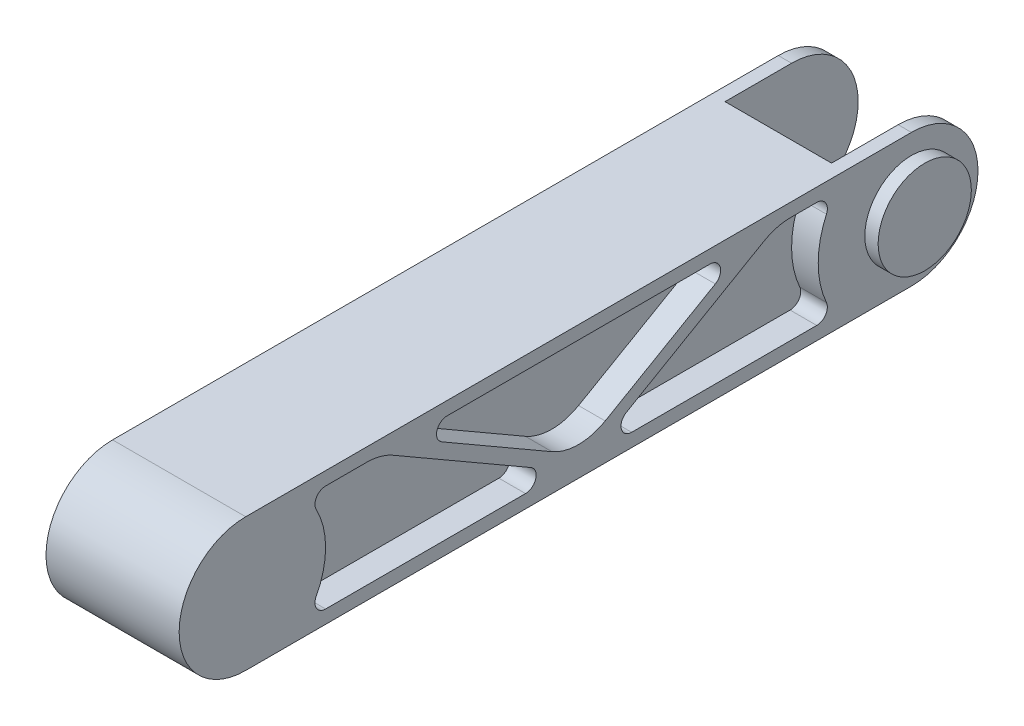
SolidWorks part; units mm, degrees
ref_plane "Front Plane" through (0, 0, 0) normal (0, 0, 1) x (1, 0, 0)
ref_plane "Top Plane" through (0, 0, 0) normal (0, 1, 0) x (1, 0, 0)
ref_plane "Right Plane" through (0, 0, 0) normal (1, 0, 0) x (0, 0, -1)
sketch "Sketch1" plane through (0, 0, 0) normal (1, 0, 0) x (0, 0, -1)
  line L1 (-125, -25) -> (125, -25)
  line L2 (-125, -25) -> (-125, 25) construction
  line L3 (-125, 25) -> (125, 25)
  line L4 (125, -25) -> (125, 25) construction
  line L5 (-125, -25) -> (125, 25) construction
  line L6 (-125, 25) -> (125, -25) construction
  arc A0 (125, 25) -> (125, -25) centre (125, 0) cw
  arc A1 (-125, 25) -> (-125, -25) centre (-125, 0) ccw
  point P0 (0, 0)
  point P8 (0, 0)
  point P9 (0, 0)
  dimension "D1" = 250
  dimension "D2" = 50
extrude "Boss-Extrude1" add sketch "Sketch1" along normal blind 25 and the other way blind 25
sketch "Sketch2" plane through (0, 25, 0) normal (0, 1, 0) x (1, 0, 0)
  line L0 (25, 150) -> (-25, 150) construction
  line L1 (-20, 200) -> (20, 200)
  line L2 (-20, 200) -> (-20, 100)
  line L3 (-20, 100) -> (20, 100)
  line L4 (20, 200) -> (20, 100)
  line L5 (-20, 200) -> (20, 100) construction
  line L6 (-20, 100) -> (20, 200) construction
  point P0 (0, 150)
  dimension "D1" = 40
  dimension "D2" = 50
extrude "Cut-Extrude1" cut sketch "Sketch2" against normal through all both and the other way through all
sketch "Sketch3" plane through (25, 0, 0) normal (1, 0, 0) x (0, 0, -1)
  line L0 (125, 25) -> (125, -25) construction
  circle A0 centre (125, 0) radius 17.5
  dimension "D1" = 35
extrude "Boss-Extrude2" add sketch "Sketch3" along normal blind 5
mirror "Mirror1" about plane through (0, 0, 0) normal (1, 0, 0) of "Boss-Extrude2"
sketch "Sketch4" plane through (25, 0, 0) normal (1, 0, 0) x (0, 0, -1)
  line L4 (125, 20) -> (-125, 20)
  line L5 (125, 20) -> (-125, 20)
  line L6 (0, 25) -> (0, -20) construction
  line L7 (-125, -20) -> (125, -20)
  line L8 (-125, -20) -> (125, -20)
  line L9 (125, 25) -> (-125, 25) construction
  line L10 (0, -20) -> (69.282, 20)
  line L11 (0, -20) -> (-69.282, 20)
  line L12 (1.25, -17.8349) -> (-68.032, 22.1651)
  line L13 (-1.25, -22.1651) -> (-88.0643, 27.9572)
  line L14 (1.25, -22.1651) -> (92.5062, 30.5217)
  line L15 (-1.25, -17.8349) -> (68.032, 22.1651)
  line L16 (1.25, -22.1651) -> (70.532, 17.8349) construction
  line L17 (-1.25, -22.1651) -> (-70.532, 17.8349) construction
  circle A0 centre (-125, 0) radius 25 construction
  arc A1 (-125, 25) -> (-125, -25) centre (-125, 0) ccw construction
  circle A2 centre (-125, 0) radius 30
  arc A5 (125, -35) -> (125, 35) centre (125, 0) ccw
  circle A6 centre (125, 0) radius 35
  point P31 (92.5062, 30.5217)
  point P34 (-88.0643, 27.9572)
  dimension "D5" = 30
  dimension "D1" = 5
  dimension "D2" = 5
  dimension "D3" = 5
  dimension "D4" = 10
  dimension "D6" = 2.5
  dimension "D7" = 2.5
  dimension "D8" = 2.5
  dimension "D9" = 2.5
extrude "Cut-Extrude2" cut sketch "Sketch4" against normal blind 10 contours A2 L8 L13 L5 | L12 L15 L5 | A6 L5 L14 L8 region at (25, -4.4098, -62.0395) region at (25, 7.6289, 0) region at (25, -3.9983, 65.1011)
fillet "Fillet1" radius 20 3 edges at (20, -17.1132, 0) (20, 20, -74.282) (20, 20, 74.282)
fillet "Fillet2" radius 4 8 edges at (20, -20, -96.2772) (20, 20, -96.2772) (20, -20, -5) (20, -20, 5) (20, -20, 102.6393) (20, 20, 102.6393) (20, 20, -64.282) (20, 20, 64.282)
mirror "Mirror2" about plane through (0, 0, 0) normal (1, 0, 0) of "Fillet2", "Fillet1", "Cut-Extrude2"
